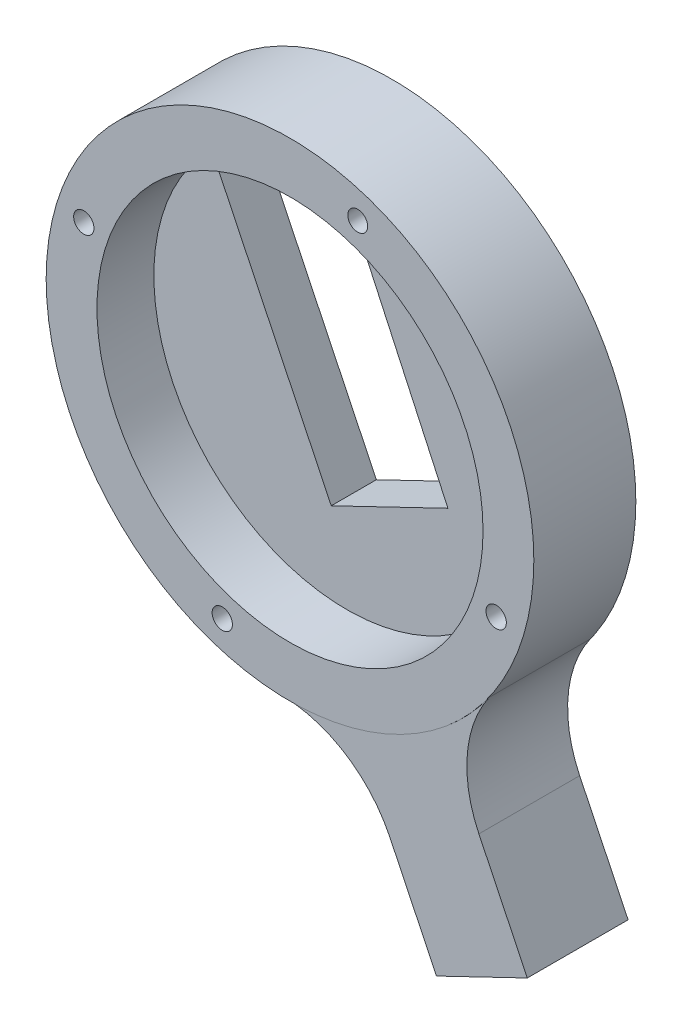
SolidWorks part; units mm, degrees
ref_plane "Front Plane" through (0, 0, 0) normal (0, 0, 1) x (1, 0, 0)
ref_plane "Top Plane" through (0, 0, 0) normal (0, 1, 0) x (1, 0, 0)
ref_plane "Right Plane" through (0, 0, 0) normal (1, 0, 0) x (0, 0, -1)
sketch "Sketch1" plane through (0, 0, 0) normal (0, 0, 1) x (1, 0, 0)
  circle A0 centre (0, 0) radius 60
  dimension "D1" = 120
extrude "Boss-Extrude1" add sketch "Sketch1" along normal blind 25.1
sketch "Sketch2" plane through (0, 0, 25.1) normal (0, 0, 1) x (1, 0, 0)
  circle A0 centre (-16.6647, -50.7331) radius 2.495
  circle A1 centre (-50.7331, 16.6647) radius 2.5
  circle A2 centre (16.6647, 50.7331) radius 2.4444
  circle A3 centre (50.7331, -16.6647) radius 2.5
sketch "Sketch3" plane through (0, 0, 25.1) normal (0, 0, 1) x (1, 0, 0)
  circle A0 centre (0, 0) radius 47.5
  dimension "D1" = 95
extrude "Cut-Extrude2" cut sketch "Sketch3" against normal blind 14
extrude "Cut-Extrude5" cut sketch "Sketch2" against normal through all both and the other way through all
sketch "Sketch6" plane through (0, 0, 0) normal (0, 0, -1) x (-1, 0, 0)
  circle A0 centre (11.9735, 47.2126) radius 3
  circle A1 centre (27.3813, 40.0293) radius 3
  circle A2 centre (-19.7177, -20.7629) radius 3
  circle A3 centre (-4.3099, -27.9462) radius 3
  dimension "D1" = 6
  dimension "D2" = 6
  dimension "D3" = 6
  dimension "D4" = 6
extrude "Cut-Extrude6" cut sketch "Sketch6" against normal blind 6
sketch "Sketch7" plane through (0, 0, 11.1) normal (0, 0, 1) x (1, 0, 0)
  line L0 (-32.7224, 32.7144) -> (-3.8455, -27.2733)
  line L1 (-3.8455, -27.2733) -> (24.8593, -13.4553)
  line L2 (24.8593, -13.4553) -> (-3.0425, 47.0016)
  line L3 (-3.0425, 47.0016) -> (-32.7224, 32.7144)
  circle A0 centre (0, 0) radius 47.1 construction
extrude "Cut-Extrude7" cut sketch "Sketch7" against normal through all both and the other way through all
ref_plane "Plane1" through (33.1075, -68.7763, 0) normal (0.4337, -0.901, 0) x (-0.901, -0.4337, 0)
sketch "Sketch8" plane through (33.1075, -68.7763, 0) normal (0.4337, -0.901, 0) x (-0.901, -0.4337, 0)
  line L1 (-13.3812, -0.0782) -> (11.4188, -0.0782)
  line L2 (-13.3812, -0.0782) -> (-13.3812, -24.8782)
  line L3 (-13.3812, -24.8782) -> (11.4188, -24.8782)
  line L4 (11.4188, -0.0782) -> (11.4188, -24.8782)
  line L5 (-13.3812, -0.0782) -> (11.4188, -24.8782) construction
  line L6 (-13.3812, -24.8782) -> (11.4188, -0.0782) construction
  point P0 (-0.9812, -12.4782)
  dimension "D1" = 24.8
  dimension "D2" = 24.8
extrude "Boss-Extrude2" add sketch "Sketch8" along normal blind 30 and the other way blind 23
fillet "Fillet1" radius 30 2 edges at (15.2601, -58.027, 12.4782) (37.426, -46.8967, 12.4782)
